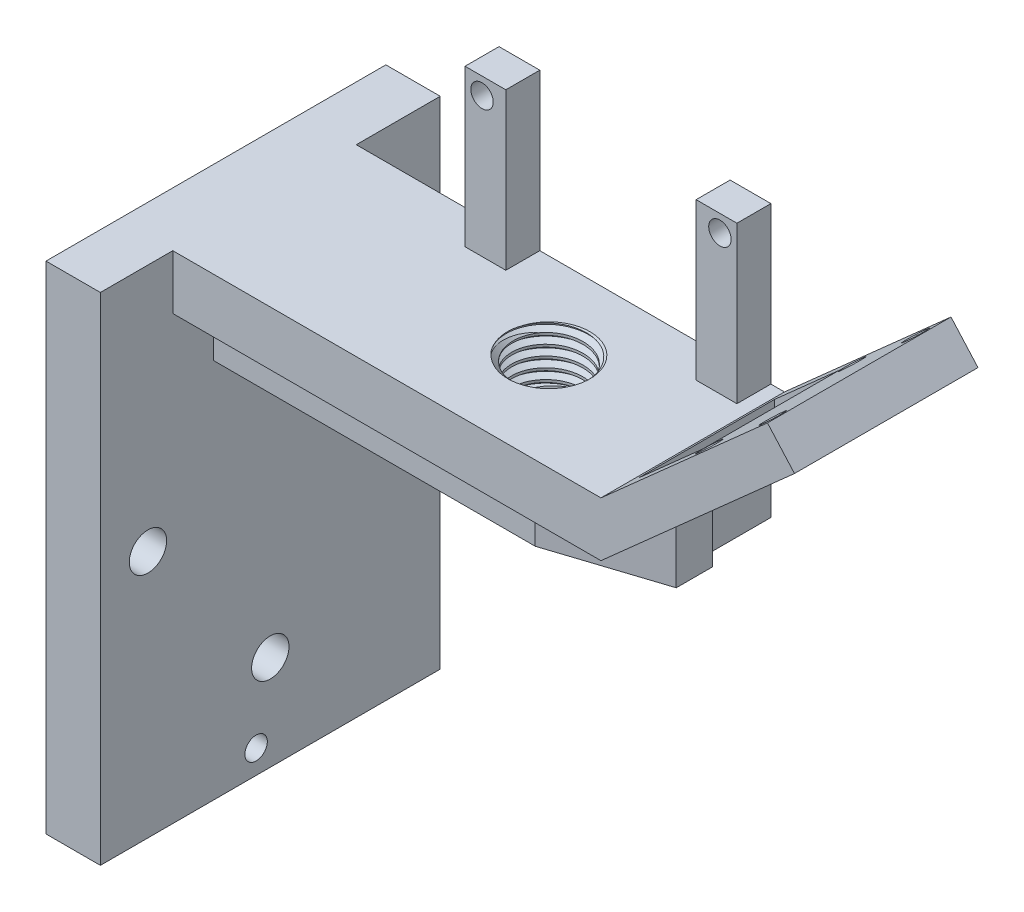
SolidWorks part; units mm, degrees
note: '?' marks a value the reader was unsure of. The reader was unsure of these and kept them because the rebuilt part matched: shared geometry of "Sketch18<3>".
ref_plane "Front Plane" through (0, 0, 0) normal (0, 0, 1) x (1, 0, 0)
ref_plane "Top Plane" through (0, 0, 0) normal (0, 1, 0) x (1, 0, 0)
ref_plane "Right Plane" through (0, 0, 0) normal (1, 0, 0) x (0, 0, -1)
ref_plane "Plane1" through (0, 10, 0) normal (0, 1, 0) x (1, 0, 0)
sketch "Sketch2" plane through (0, 10, 0) normal (0, 1, 0) x (1, 0, 0)
  line L0 (10.15, 21) -> (33.86, 21)
  line L2 (42.88, 4.07) -> (30.33, 0)
  line L3 (30.33, 0) -> (0, 0)
  line L6 (0, 0) -> (0, 10)
  line L7 (0, 10) -> (10.15, 21)
  line L8 (33.86, 21) -> (44.46, 11.73)
  line L10 (45.9955, 5.0804) -> (42.88, 4.07)
  line L11 (44.46, 11.73) -> (45.9955, 10.3871)
  line L12 (45.9955, 10.3871) -> (45.9955, 5.0804)
  arc A5 (44.46, 11.73) -> (42.88, 4.07) centre (41.5017, 8.3472) cw construction
  circle A6 centre (41.5017, 8.3472) radius 2.1 construction
  dimension "D10" = 4.2
  dimension "D1" = 10
  dimension "D2" = 30.33
  dimension "D3" = 11
  dimension "D4" = 10.15
  dimension "D5" = 23.71
  dimension "D6" = 4.07
  dimension "D7" = 12.55
  dimension "D8" = 9.27
  dimension "D9" = 10.6
extrude "Boss-Extrude2" add sketch "Sketch2" along normal blind 17 separate body
fillet "Fillet4" radius 2 1 edges at (33.86, 18.5, -21)
sketch "Sketch5" plane through (0, 10, 0) normal (0, -1, 0) x (1, 0, 0)
  line L0 (0, -10) -> (0, 0) construction
  line L1 (0, 0) -> (30.33, 0) construction
  circle A0 centre (4.5, -8.35) radius 2.1
  circle A1 centre (41.5, -8.35) radius 2.1
  dimension "D1" = 4.2
  dimension "D2" = 4.2
  dimension "D3" = 41.5
  dimension "D4" = 4.5
  dimension "D5" = 8.35
extrude "Cut-Extrude3" cut sketch "Sketch5" against normal blind 10 and the other way through all
sketch "Sketch6" plane through (0, 10, 0) normal (0, -1, 0) x (1, 0, 0)
  line L0 (6.75, -3.5) -> (29.7767, -3.5)
  line L1 (29.7767, -3.5) -> (37.6334, -6.048)
  line L2 (6.75, -3.5) -> (6.75, -4.4529)
  line L3 (30.33, 0) -> (45.9955, -5.0804) construction
  line L4 (0, 0) -> (30.33, 0) construction
  line L5 (11.6828, -17.5) -> (32.5455, -17.5)
  line L6 (32.5455, -17.5) -> (38.8497, -11.9868)
  line L7 (11.6828, -17.5) -> (6.8057, -12.2144)
  line L8 (10.15, -21) -> (0, -10) construction
  line L9 (45.9955, -10.3871) -> (34.4254, -20.5055) construction
  line L10 (33.1088, -21) -> (10.15, -21) construction
  line L11 (0, -10) -> (0, 0) construction
  arc A0 (6.8057, -12.2144) -> (6.75, -4.4529) centre (4.5, -8.35) ccw
  arc A1 (37.6334, -6.048) -> (38.8497, -11.9868) centre (41.5, -8.35) ccw
  dimension "D1" = 9
  dimension "D2" = 9
  dimension "D3" = 3.5
  dimension "D4" = 3.5
  dimension "D5" = 3.5
  dimension "D6" = 3.5
  dimension "D7" = 3.5
  dimension "D8" = 6.75
extrude "Cut-Extrude4" cut sketch "Sketch6" against normal through all
fillet "Fillet5" radius 1 4 edges at (6.75, 27, -3.9764) (6.75, 18.5, -4.4529) (6.75, 18.5, -3.5) (6.75, 10, -3.9764)
fillet "Fillet6" radius 1 6 edges at (6.8057, 18.5, -12.2144) (11.6828, 18.5, -17.5) (32.5455, 18.5, -17.5) (38.8497, 18.5, -11.9868) (37.6334, 18.5, -6.048) (29.7767, 18.5, -3.5)
sketch "Sketch7" plane through (0, 0, -21) normal (0, 0, -1) x (-1, 0, 0)
  line L0 (-33.1088, 27) -> (-10.15, 27) construction
  line L1 (-36.9955, 23.5) -> (-9, 23.5)
  line L2 (-36.9955, 23.5) -> (-36.9955, 13.5)
  line L3 (-36.9955, 13.5) -> (-9, 13.5)
  line L4 (-9, 23.5) -> (-9, 13.5)
  line L5 (-33.1088, 10) -> (-10.15, 10) construction
  line L6 (-45.9955, 27) -> (-45.9955, 10) construction
  line L8 (-4.5, 27) -> (-4.5, 10) construction
  dimension "D1" = 3.5
  dimension "D2" = 3.5
  dimension "D3" = 9
  dimension "D4" = 4.5
extrude "Cut-Extrude5" cut sketch "Sketch7" along normal blind 8 from surface at -21 starting at face at (15.165, 18.5, 0)
ref_plane "Plane2" through (0, 0, -21) normal (0, 0, 1) x (1, 0, 0)
sketch "Sketch11" plane through (0, 0, -21) normal (0, 0, 1) x (1, 0, 0)
  line L0 (0, 27) -> (0, 10) construction
  line L1 (45.9955, 27) -> (-25, 27)
  line L2 (45.9955, 27) -> (45.9955, 19)
  line L3 (45.9955, 19) -> (-25, 19)
  line L4 (-25, 27) -> (-25, 19)
  line L7 (33.1088, 27) -> (10.15, 27) construction
  line L11 (45.9955, 27) -> (45.9955, 10) construction
  dimension "D1" = 8
  dimension "D2" = 25
extrude "Boss-Extrude4" add sketch "Sketch11" along normal blind 27
sketch "Sketch20" plane through (0, 27, 0) normal (0, 1, 0) x (1, 0, 0)
  line L0 (41.5, 8.35) -> (4.5, 8.35) construction
  point P4 (24, 8.35)
  dimension "D1" = 19.5
hole_wizard "M12x1.5 Tapped Hole2" positions "Sketch20" profile "Sketch23" tap size "M12x1.5" standard "ANSI Metric" end condition through all
sketch "Sketch23" plane through (24, 27, -8.35) normal (1, 0, 0) x (0, 0, 1)
  line L0 (0, 0) -> (0, 17)
  line L1 (0, 17) -> (5.25, 17)
  line L2 (5.25, 17) -> (5.25, 0.775)
  line L3 (5.25, 0.775) -> (6.025, 0)
  line L5 (6.025, 0) -> (0, 0)
  line L6 (-5.25, 0.775) -> (-6.025, 0) construction
  line L11 (0, -6.35) -> (0, 107.95) construction
  dimension "Thru Tap Drill Dia." = 10.5
  dimension "Thru Tap Drill Depth" = 17
  dimension "Near C'Sink Dia." = 12.05
  dimension "Near C'Sink Angle" = 90
cosmetic thread "Hole Thread3" parameters "D2"=12
thread "Thread1" pitch 1.5 start angle 0, offset 2, length 0, pitch 1.5, diameter 10.5
ref_plane "Plane4" through (18.75, 29, -8.35) normal (0, 0, 1) x (-1, 0, 0)
sketch "Thread Profile1" plane through (18.75, 29, -8.35) normal (0, 0, 1) x (-1, 0, 0)
  line L0 (0, 0) -> (0, 1.5) construction
  line L1 (0, 0) -> (0.8119, 0.4687)
  line L2 (0.8119, 0.4687) -> (0.8119, 0.6562)
  line L3 (0.8119, 0.6562) -> (0, 1.125)
  line L4 (0.8119, 0.5625) -> (0, 0.5625) construction
  line L11 (0, 0) -> (0, 1.125)
  point P2 (0, 0)
  dimension "Pitch" = 1.5
  dimension "Profile_Angle" = 60
  dimension "Profile_Land" = 0.1875
  dimension "Profile_Height" = 0.8119
ref_axis "Axis1" through (24, 18.9882, -8.35) along (0, 1, 0)?
ref_plane "Plane6" through (0, 0, -8.35) normal (0, 0, 1) x (1, 0, 0)
sketch "Sketch18" plane through (0, 0, -21) normal (0, 0, 1) x (1, 0, 0)
  line L1 (4, 10) -> (44, 10)
  line L2 (4, 10) -> (4, 50)
  line L3 (4, 50) -> (10, 50)
  line L4 (44, 10) -> (44, 50)
  line L6 (24, 18.9882) -> (24, 26.23) construction
  line L12 (12.7834, 10) -> (-12.7834, 10) construction
  line L13 (4, 27) -> (16.9955, 27)
  line L15 (38, 50) -> (44, 50)
  line L17 (10, 50) -> (10, 27)
  line L18 (10, 27) -> (38, 27)
  line L19 (38, 50) -> (38, 27)
  line L20 (45.9955, 27) -> (-25, 27) construction
  point P9 (10.4978, 27)
  point P16 (10.4978, 27)
  dimension "D1" = 40
  dimension "D2" = 40
  dimension "D3" = 6
  dimension "D4" = 20
extrude "Boss-Extrude9" add sketch "Sketch18" along normal up to body contours L13 L2 L1 L4
extrude "Boss-Extrude10" add sketch "Sketch18<3>" along normal blind 5 contours L2 L13 L4 L3 | L15 L19 L13 L4
sketch "Sketch18<3>" plane through (0, 0, -21) normal (0, 0, 1) x (1, 0, 0) same geometry as "Sketch18"
ref_plane "Plane5" through (0, 80, 0) normal (0, 1, 0) x (1, 0, 0)
sketch "Sketch27" plane through (0, 0, -21) normal (0, 0, 1) x (1, 0, 0)
  line L0 (6.5, 12.5) -> (6.5, 47.5) construction
  line L1 (6.5, 47.5) -> (41.5, 47.5) construction
  line L2 (41.5, 47.5) -> (41.5, 12.5) construction
  line L3 (41.5, 12.5) -> (6.5, 12.5) construction
  line L4 (4, 50) -> (6.5, 47.5) construction
  line L5 (6.5, 12.5) -> (4, 10) construction
  line L7 (41.5, 12.5) -> (44, 10) construction
  circle A0 centre (6.5, 47.5) radius 1.65
  circle A1 centre (6.5, 12.5) radius 1.65
  circle A2 centre (41.5, 12.5) radius 1.65
  circle A3 centre (41.5, 47.5) radius 1.65
  dimension "D1" = 3.3
  dimension "D2" = 35
extrude "Cut-Extrude7" cut sketch "Sketch27" along normal blind 5
sketch "Sketch28" plane through (0, 0, -8.35) normal (0, 0, 1) x (1, 0, 0)
  line L0 (4, 27) -> (-25, 27) construction
  line L1 (-25, 27) -> (-17, 27)
  line L2 (-25, 27) -> (-25, -46)
  line L3 (-25, -46) -> (-17, -46)
  line L4 (-17, 27) -> (-17, -46)
  dimension "D1" = 8
  dimension "D2" = 73
extrude "Boss-Extrude11" add sketch "Sketch28" along normal blind 25 and the other way blind 25
sketch "Sketch29" plane through (0, 19, -40) normal (0, -1, 0) x (1, 0, 0)
  line L0 (-17, 40) -> (0, 40)
  line L5 (0, 40) -> (0, 30)
  line L6 (0, 30) -> (4, 25.665)
  line L7 (4, 25.665) -> (4, 19)
  line L8 (46.75, 19) -> (-46.75, 19) construction
  line L9 (4, 25.665) -> (4, 19) construction
  line L10 (4, 19) -> (-17, 19)
  line L11 (-17, 6.65) -> (-17, 56.65) construction
  line L12 (-17, 19) -> (-17, 40)
extrude "Boss-Extrude13" add sketch "Sketch29" along normal up to surface (9 mm away) up to plane "Plane1"
sketch "Sketch30" plane through (-17, 0, -7) normal (1, 0, 0) x (0, 0, -1)
  line L12 (26.35, -46) -> (-23.65, 27) construction
  line L13 (1.35, -32) -> (1.35, 13) construction
  line L14 (1.35, 18.9882) -> (1.35, 26.23) construction
  line L17 (1.35, 3.983) -> (1.35, -3.983) construction
  line L19 (-16.65, -9.5) -> (19.35, -9.5) construction
  circle A8 centre (19.35, -9.5) radius 2.75
  circle A9 centre (-16.65, -9.5) radius 2.75
  circle A10 centre (1.35, 13) radius 2.75
  circle A11 centre (1.35, -32) radius 2.75
  point P15 (1.35, -9.5)
  point P22 (1.35, -9.5)
  dimension "D1" = 36
  dimension "D2" = 45
  dimension "D7" = 5.5
extrude "Cut-Extrude8" cut sketch "Sketch30" against normal blind 25
sketch "Sketch31" plane through (0, 0, -8.35) normal (0, 0, 1) x (1, 0, 0)
  line L0 (27.5, 80) -> (-27.5, 80) construction
  line L1 (24, 18.9882) -> (24, 26.23) construction
  line L2 (24, 80) -> (91.7306, 3.8773) construction
  line L3 (45.9955, 27) -> (60.0392, 39.4954)
  line L5 (64.012, 35.0303) -> (45.9955, 19)
  line L6 (45.9955, 19) -> (45.9955, 27)
  line L7 (60.0392, 39.4954) -> (70.4984, 48.8016)
  line L8 (70.4984, 48.8016) -> (74.4713, 44.3364)
  line L9 (74.4713, 44.3364) -> (64.012, 35.0303)
  point P0 (24, 80)
  dimension "D1" = 14
  dimension "D2" = 5
extrude "Boss-Extrude14" add sketch "Sketch31" against normal up to surface and the other way up to surface
sketch "Sketch32" plane through (0, 0, 0) normal (0, 1, 0) x (1, 0, 0)
  line L0 (45.9955, -6) -> (45.9955, 21) construction
  line L1 (57.4984, 17.5) -> (47.9955, 17.5)
  line L2 (57.4984, 17.5) -> (57.4984, -2.5)
  line L3 (57.4984, -2.5) -> (47.9955, -2.5)
  line L4 (47.9955, 17.5) -> (47.9955, -2.5)
  line L5 (47.9955, -2.5) -> (45.9955, -6) construction
  line L6 (47.9955, 17.5) -> (45.9955, 21) construction
  line L9 (70.4984, -6) -> (70.4984, 21) construction
  dimension "D1" = 20
  dimension "D2" = 13
  dimension "D3" = 2
extrude "Cut-Extrude9" cut sketch "Sketch32" along normal through all
sketch "Sketch34" plane through (6.9151, -7.772, 0) normal (-0.6647, 0.7471, 0) x (0.7471, 0.6647, 0)
  line L0 (85.1081, -6) -> (85.1081, 21) construction
  line L5 (69.6081, 18) -> (82.1081, 18) construction
  line L6 (69.6081, 18) -> (69.6081, -3) construction
  line L7 (69.6081, -3) -> (82.1081, -3) construction
  line L8 (82.1081, 18) -> (82.1081, -3) construction
  line L9 (82.1081, 7.5) -> (85.1081, 7.5) construction
  circle A4 centre (82.1081, 18) radius 1.65
  circle A5 centre (69.6081, 18) radius 1.65
  circle A6 centre (69.6081, -3) radius 1.65
  circle A7 centre (82.1081, -3) radius 1.65
  dimension "D1" = 3.3
  dimension "D2" = 3
  dimension "D3" = 21
  dimension "D4" = 12.5
extrude "Cut-Extrude10" cut sketch "Sketch34" against normal blind 5
sketch "Sketch35" plane through (-17, 0, -17) normal (1, 0, 0) x (0, 0, -1)
  line L0 (16.35, -46) -> (-33.65, -46) construction
  line L2 (-10.7352, -42.5) -> (-10.7352, 6.5) construction
  line L3 (16.35, -46) -> (16.35, 27) construction
  circle A1 centre (-10.7352, 6.5) radius 1.65
  circle A3 centre (-10.7352, -42.5) radius 1.65
  dimension "D1" = 3.5
  dimension "D2" = 49
  dimension "D4" = 3.3
  dimension "D3" = 27.0852
extrude "Cut-Extrude11" cut sketch "Sketch35" against normal blind 5
